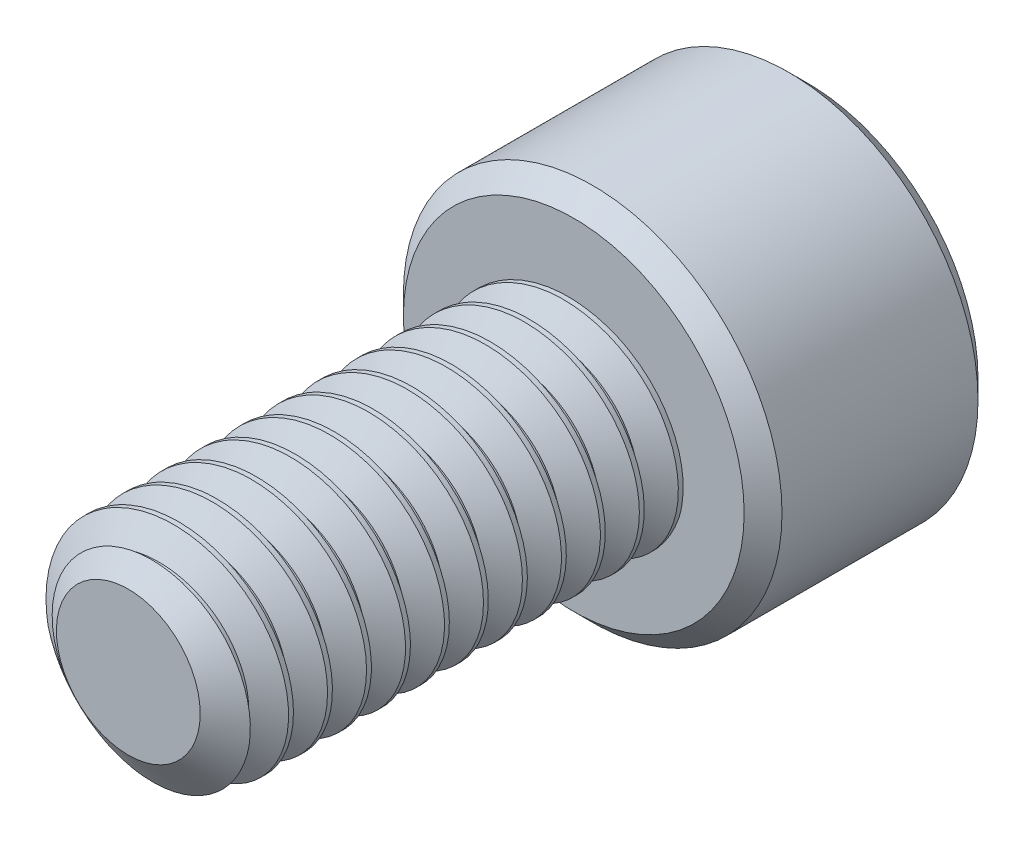
SolidWorks part; units mm, degrees
material "Nylon 6/10"
ref_plane "Front Plane" through (0, 0, 0) normal (0, 0, 1) x (1, 0, 0)
ref_plane "Top Plane" through (0, 0, 0) normal (0, 1, 0) x (1, 0, 0)
ref_plane "Right Plane" through (0, 0, 0) normal (1, 0, 0) x (0, 0, -1)
ref_axis "Centre Axis" through (0, 0, -13.0568) along (0, 0, 1)
sketch "Sketch1" plane through (0, 0, 0) normal (0, 0, 1) x (1, 0, 0)
  circle A0 centre (0, 0) radius 2
  dimension "OD" = 4
extrude "Extrude1" add sketch "Sketch1" against normal blind 8
sketch "Sketch2" plane through (0, 0, 0) normal (0, 0, 1) x (1, 0, 0)
  circle A0 centre (0, 0) radius 2 construction
  circle A1 centre (0, 0) radius 2
curve "Helix/Spiral1" pitch 0.7 height 8.7 radius 2 centre (0, 0, 0) axis (0, 0, -1) start towards (0, 1, 0) parameters "pitch"=0.7
sketch "Sketch3" plane through (0, 0, 0) normal (1, 0, 0) x (0, 0, -1)
  line L0 (-0.6125, 2) -> (-0.35, 1.5453)
  line L1 (-0.35, 1.5453) -> (-0.2625, 1.5453)
  line L2 (-0.2625, 1.5453) -> (0, 2)
  line L3 (-0.6125, 2) -> (0, 2)
  line L4 (-0.3062, 2) -> (-0.3062, 1.5453) construction
  line L5 (-0.4812, 1.7727) -> (-0.1312, 1.7727) construction
  line L6 (0, 2) -> (0, -2) construction
  dimension "D1" = 0.0875
  dimension "D2" = 0.35
  dimension "D3" = 60
sweep "Cut-Sweep1" cut profiles "Sketch3" path "Helix/Spiral1" align with end faces yes
sketch "Sketch4" plane through (0, 0, 0) normal (1, 0, 0) x (0, 0, -1)
  line L0 (0.4962, 2) -> (0, 1.2913)
  line L1 (0, 1.2913) -> (0, 2)
  line L2 (0.4962, 2) -> (0, 2)
  line L3 (-0.6125, 2) -> (0, 2) construction
  line L4 (0, 0) -> (7.0209, 0) construction
  dimension "D1" = 55
  dimension "D2" = 0.254
revolve "Cut-Revolve1" cut sketch "Sketch4" angle 360 about L4
sketch "Sketch6" plane through (0, 0, -8) normal (0, 0, -1) x (-1, 0, 0)
  circle A0 centre (0, 0) radius 3.4
  dimension "head dia" = 6.8
extrude "Extrude2" add sketch "Sketch6" along normal blind 4.2
sketch "Sketch7" plane through (0, 0, -12.2) normal (0, 0, -1) x (-1, 0, 0)
  line L1 (0, 2.0622) -> (-1.7859, 1.0311)
  line L2 (-1.7859, 1.0311) -> (-1.7859, -1.0311)
  line L3 (-1.7859, -1.0311) -> (0, -2.0622)
  line L4 (0, -2.0622) -> (1.7859, -1.0311)
  line L5 (1.7859, -1.0311) -> (1.7859, 1.0311)
  line L6 (1.7859, 1.0311) -> (0, 2.0622)
  circle A0 centre (0, 0) radius 1.7859 construction
  dimension "hex dia" = 3.5719
extrude "Cut-Extrude1" cut sketch "Sketch7" against normal blind 2.6789
sketch "Sketch8" plane through (0, 0, -12.2) normal (0, 0, -1) x (-1, 0, 0)
  circle A0 centre (0, 0) radius 2.0622
extrude "Cut-Extrude2" cut sketch "Sketch8" against normal through all draft 45
chamfer "Chamfer1" distance 0.34 angle 45 2 edges at (-3.4, 0, -12.2) (-3.4, 0, -8)
sketch "Sketch10" plane through (0, 0, -8) normal (0, 0, 1) x (1, 0, 0)
  circle A1 centre (0, 0) radius 2
  circle A2 centre (0, 0) radius 2
  dimension "D1" = 0
ref_plane "Plane1" through (0, 0, -38.1) normal (0, 0, 1) x (1, 0, 0)
extrude "partial thread" [suppressed] add sketch "Sketch10" along normal up to surface (12.7 mm away) separate body up to plane "Plane1"
chamfer "Chamfer2" [suppressed] distance 0.08 angle 45
combine bodies "Combine1" [suppressed] operation type add bodies to combine 107 108
sketch "Sketch9" plane through (0, 0, 0) normal (1, 0, 0) x (0, 0, -1)
  line L0 (0, 2) -> (0, -2) construction
  line L1 (1.75, 2) -> (1.75, -2) construction
  dimension "D1" = 1.75
equation "\"D3@Helix/Spiral1\" = \"screw length@Extrude1\"+\"pitch@Helix/Spiral1\""
equation "\"D1@Sketch3\" = \"pitch@Helix/Spiral1\"*.125"
equation "\"D2@Sketch3\" = \"pitch@Helix/Spiral1\"*.5"
equation "\"D1@Cut-Extrude1\" = \"hex dia@Sketch7\"*.75"
equation "\"D1@Chamfer1\" = \"head dia@Sketch6\"*.05"
equation "\"D1@Sketch9\" = \"pitch@Helix/Spiral1\"*2.5"
equation "\"D1@Chamfer2\"=\"OD@Sketch1\"*.02"
